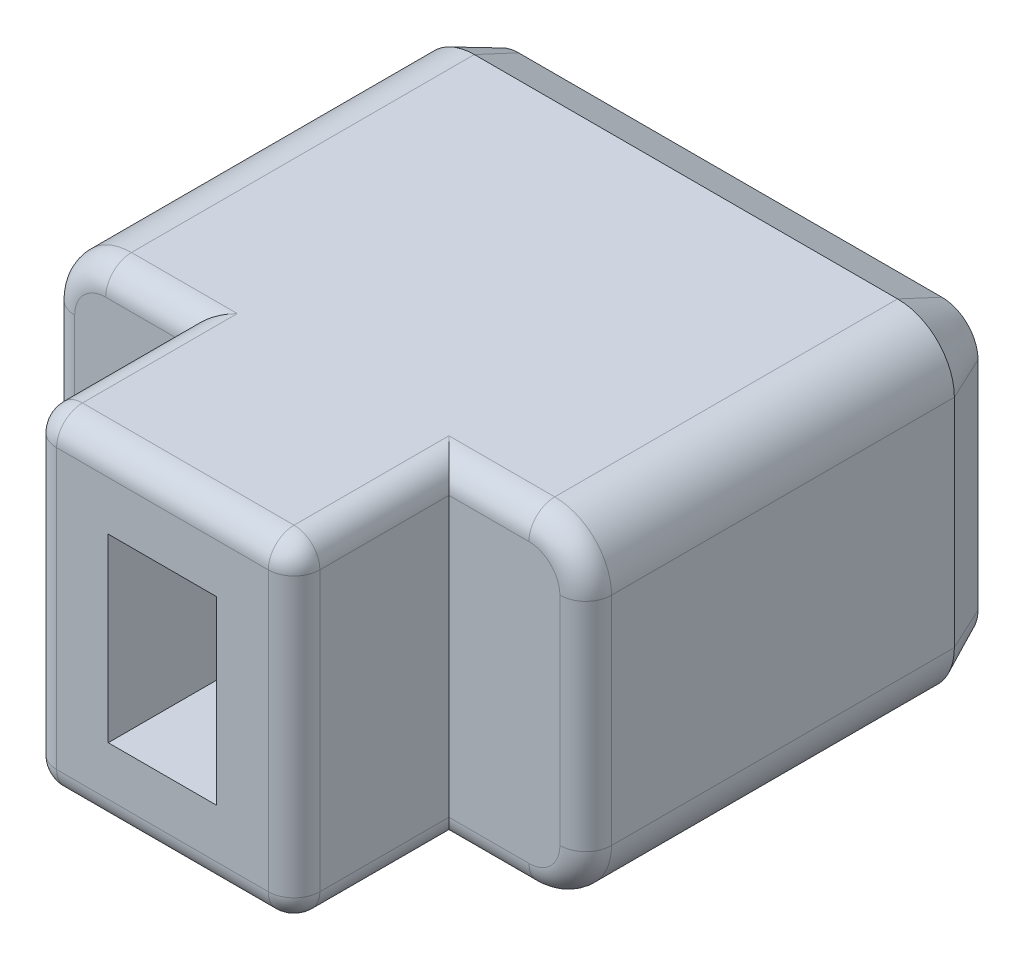
SolidWorks part; units mm, degrees
ref_plane "Plan de face" through (0, 0, 0) normal (0, 0, 1) x (1, 0, 0)
ref_plane "Plan de dessus" through (0, 0, 0) normal (0, 1, 0) x (1, 0, 0)
ref_plane "Plan de droite" through (0, 0, 0) normal (1, 0, 0) x (0, 0, -1)
sketch "Esquisse2" plane through (0, 0, 0) normal (0, 0, 1) x (1, 0, 0)
  line L1 (1.1, 0) -> (9.3, 0)
  line L2 (0, 1.1) -> (0, 5.3)
  line L3 (1.1, 6.4) -> (9.3, 6.4)
  line L4 (10.4, 1.1) -> (10.4, 5.3)
  arc A0 (9.3, 6.4) -> (10.4, 5.3) centre (9.3, 5.3) cw
  arc A1 (9.3, 0) -> (10.4, 1.1) centre (9.3, 1.1) ccw
  arc A2 (1.1, 0) -> (0, 1.1) centre (1.1, 1.1) cw
  arc A3 (0, 5.3) -> (1.1, 6.4) centre (1.1, 5.3) cw
  point P7 (10.4, 6.4)
  point P12 (0, 0)
  point P15 (0, 6.4)
  dimension "D3" = 1.1
  dimension "D1" = 10.4
  dimension "D2" = 6.4
extrude "Boss.-Extru.1" add sketch "Esquisse2" along normal blind 11
sketch "Esquisse3" plane through (0, 0, 11) normal (0, 0, 1) x (1, 0, 0)
  line L0 (0, 5.3) -> (0, 1.1) construction
  line L1 (4.15, 4.95) -> (6.25, 4.95)
  line L2 (4.15, 4.95) -> (4.15, 1.45)
  line L3 (4.15, 1.45) -> (6.25, 1.45)
  line L4 (6.25, 4.95) -> (6.25, 1.45)
  line L5 (10.4, 1.1) -> (10.4, 5.3) construction
  line L6 (9.3, 6.4) -> (1.1, 6.4) construction
  line L7 (1.1, 0) -> (9.3, 0) construction
  dimension "D1" = 2.1
  dimension "D2" = 3.5
  dimension "D3" = 4.15
  dimension "D4" = 4.15
  dimension "D5" = 1.45
  dimension "D6" = 1.45
extrude "Enlèv. mat.-Extru.1" cut sketch "Esquisse3" against normal blind 3
sketch "Esquisse4" plane through (0, 0, 11) normal (0, 0, 1) x (1, 0, 0)
  line L0 (2.65, 6.4) -> (2.65, 0)
  line L1 (9.3, 6.4) -> (1.1, 6.4) construction
  line L2 (1.1, 0) -> (9.3, 0) construction
  line L3 (2.65, 0) -> (7.75, 0)
  line L4 (7.75, 0) -> (7.75, 6.4)
  line L5 (7.75, 6.4) -> (2.65, 6.4)
  line L6 (4.15, 4.95) -> (4.15, 1.45) construction
  line L7 (6.25, 1.45) -> (6.25, 4.95) construction
  dimension "D1" = 1.5
  dimension "D2" = 1.5
extrude "Enlèv. mat.-Extru.2" cut sketch "Esquisse4" against normal blind 3 flip side to cut
fillet "Congé1" radius 0.5 18 edges at (8.525, 0, 8) (10.0778, 0.3222, 8) (10.4, 3.2, 8) (10.0778, 6.0778, 8) (1.875, 6.4, 8) (0.3222, 6.0778, 8) (1.875, 0, 8) (0.3222, 0.3222, 8) (7.75, 6.4, 9.5) (2.65, 6.4, 9.5) (7.75, 0, 9.5) (2.65, 0, 9.5) (2.65, 3.2, 11) (5.2, 6.4, 11) (7.75, 3.2, 11) (5.2, 0, 11) (8.525, 6.4, 8) (0, 3.2, 8)
chamfer "Chanfrein1" distance 0.4 angle 65 8 edges at (5.2, 0, 0) (10.0778, 0.3222, 0) (0.3222, 0.3222, 0) (10.4, 3.2, 0) (0, 3.2, 0) (10.0778, 6.0778, 0) (0.3222, 6.0778, 0) (5.2, 6.4, 0) first distance on face at (5.2, 3.2, 0)
sketch "Esquisse5" plane through (0, 0, 0) normal (0, 0, -1) x (-1, 0, 0)
  line L0 (-0.4, 5.3) -> (-10, 5.3) construction
  arc A0 (-9.3, 6) -> (-10, 5.3) centre (-9.3, 5.3) ccw construction
  text T0 "4" font "Century Gothic" height 4
extrude "Enlèv. mat.-Extru.3" cut sketch "Esquisse5" against normal blind 0.3
extrude "Boss.-Extru.2" add sketch "Esquisse5<2>" along normal blind 0.3 separate body
sketch "Esquisse5<2>" plane through (0, 0, 0) normal (0, 0, -1) x (-1, 0, 0) same geometry as "Esquisse5"
